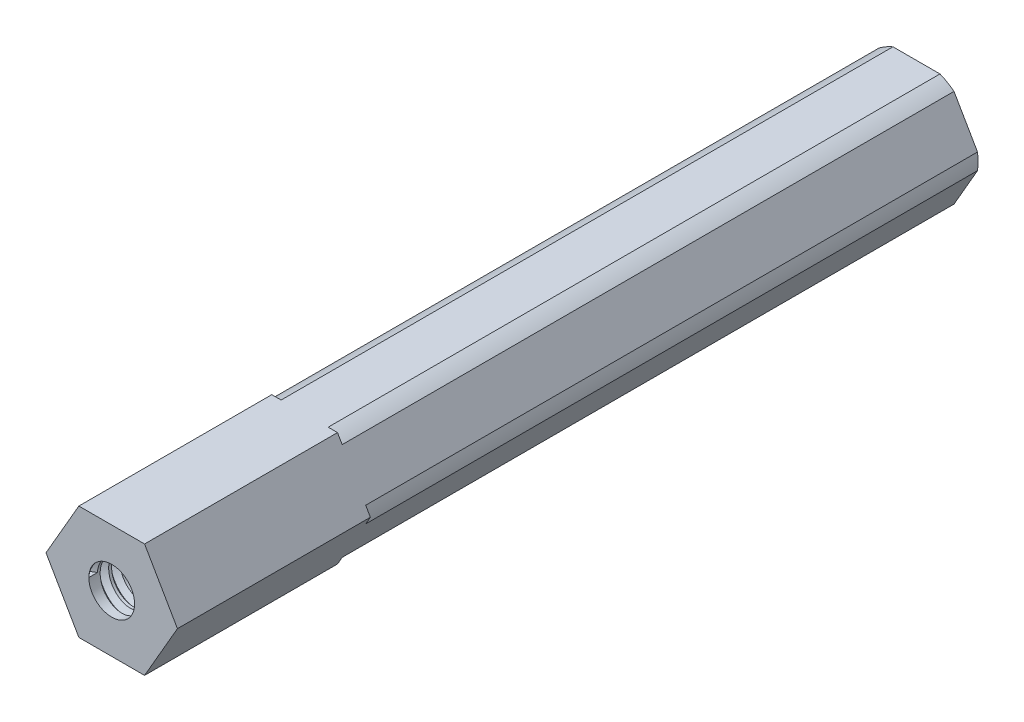
SolidWorks part; units mm, degrees
material "7075-T6 (SN)"
ref_plane "Alzado" through (0, 0, 0) normal (0, 0, 1) x (1, 0, 0)
ref_plane "Planta" through (0, 0, 0) normal (0, 1, 0) x (1, 0, 0)
ref_plane "Vista lateral" through (0, 0, 0) normal (1, 0, 0) x (0, 0, -1)
sketch "Croquis2" plane through (0, 0, 0) normal (0, 0, 1) x (1, 0, 0)
  line L1 (3.6662, -6.35) -> (7.3323, 0)
  line L2 (7.3323, 0) -> (3.6662, 6.35)
  line L3 (3.6662, 6.35) -> (-3.6662, 6.35)
  line L4 (-3.6662, 6.35) -> (-7.3323, 0)
  line L5 (-7.3323, 0) -> (-3.6662, -6.35)
  line L6 (-3.6662, -6.35) -> (3.6662, -6.35)
  circle A0 centre (0, 0) radius 6.35 construction
  dimension "D1" = 12.7
extrude "Extrusión Hex Profile" add sketch "Croquis2" along normal mid plane 89.789
sketch "Croquis3" plane through (0, 0, 0) normal (0, 0, 1) x (1, 0, 0)
  circle A0 centre (0, 0) radius 2.5527
  dimension "D1" = 5.1054
extrude "Tap Hole 1" cut sketch "Croquis3" against normal blind 19.05 from surface starting at face at (0, 0, 44.8945)
extrude "Tap Hole 2" cut sketch "Croquis3<3>" along normal blind 19.05 from surface starting at face at (0, 0, -44.8945)
sketch "Croquis3<3>" plane through (0, 0, 0) normal (0, 0, 1) x (1, 0, 0) same geometry as "Croquis3"
sketch "Croquis7" plane through (0, 0, 0) normal (0, 0, 1) x (1, 0, 0)
  circle A0 centre (0, 0) radius 6.8707
  dimension "D1" = 13.7414
extrude "ThunderHex" cut sketch "Croquis7" along normal offset from surface (68.2625 mm away) 21.5265 from surface flip side to cut up to face at (2.5527, 0, 44.8945) starting at face at (2.5527, 0, -44.8945)
sketch "Croquis8" plane through (0, 0, 0) normal (0, 1, 0) x (1, 0, 0)
  line L0 (0, -44.8945) -> (-5.5562, -44.8945) construction
  line L1 (3.6662, -44.8945) -> (-3.6662, -44.8945) construction
  line L3 (0, -44.8945) -> (0, 0) construction
  line L4 (-5.5562, -44.8945) -> (-6.35, -44.1008)
  line L5 (-6.35, -44.1008) -> (-6.35, -43.307)
  line L6 (-6.35, -43.307) -> (-5.9055, -43.307)
  line L7 (-5.9055, -43.307) -> (-5.9055, -41.7195)
  line L8 (-5.9055, -41.7195) -> (-12.7, -41.7195)
  line L9 (-12.7, -41.7195) -> (-12.7, -44.8945)
  line L10 (-12.7, -44.8945) -> (-5.5562, -44.8945)
  line L11 (-3.6662, -44.8945) -> (-7.3323, -44.8945) construction
  dimension "D1" = 11.811
  dimension "D2" = 12.7
  dimension "D3" = 45
  dimension "D4" = 0.7937
  dimension "D6" = 0.7937
  dimension "D7" = 3.175
  dimension "D8" = 25.4
revolve "Retaining Ring 1" [suppressed] cut sketch "Croquis8" angle 360 about L3
sketch "Croquis9" plane through (0, 0, 0) normal (0, -1, 0) x (1, 0, 0)
  line L0 (0, -44.8945) -> (-5.5562, -44.8945) construction
  line L3 (0, -44.8945) -> (0, 0) construction
  line L4 (-5.5562, -44.8945) -> (-6.35, -44.1008)
  line L5 (-6.35, -44.1008) -> (-6.35, -43.307)
  line L6 (-6.35, -43.307) -> (-5.9055, -43.307)
  line L7 (-5.9055, -43.307) -> (-5.9055, -41.7195)
  line L8 (-5.9055, -41.7195) -> (-12.7, -41.7195)
  line L9 (-12.7, -41.7195) -> (-12.7, -44.8945)
  line L10 (-12.7, -44.8945) -> (-5.5562, -44.8945)
  line L12 (-2.6237, -44.8945) -> (2.6237, -44.8945) construction
  line L13 (-6.8111, -44.8945) -> (-4.1874, -44.8945) construction
  dimension "D1" = 11.811
  dimension "D2" = 12.7
  dimension "D3" = 45
  dimension "D4" = 0.7937
  dimension "D6" = 0.7937
  dimension "D7" = 3.175
  dimension "D8" = 25.4
revolve "Retaining Ring 2" [suppressed] cut sketch "Croquis9" angle 360 about L3
sketch "Croquis10" plane through (0, 0, 0) normal (0, 1, 0) x (1, 0, 0)
  line L0 (0, -44.8945) -> (0, 0) construction
  line L1 (3.6662, -44.8945) -> (-3.6662, -44.8945) construction
  line L2 (0, -44.8945) -> (-5.5562, -44.8945) construction
  line L3 (-3.6662, -44.8945) -> (-7.3323, -44.8945) construction
  line L4 (-5.5562, -44.8945) -> (-6.35, -44.1008)
  line L5 (-6.35, -44.1008) -> (-6.35, -36.9443)
  line L6 (-6.35, -36.9443) -> (-9.525, -36.9443)
  line L7 (-9.525, -36.9443) -> (-9.525, -44.8945)
  line L8 (-9.525, -44.8945) -> (-5.5562, -44.8945)
  dimension "D2" = 12.7
  dimension "D1" = 45
  dimension "D3" = 0.7937
  dimension "D4" = 7.9502
  dimension "D5" = 19.05
revolve "Round End 1" [suppressed] cut sketch "Croquis10" angle 360 about L0
sketch "Croquis12" plane through (0, 0, 0) normal (0, -1, 0) x (1, 0, 0)
  line L0 (0, -44.8945) -> (0, 0) construction
  line L2 (0, -44.8945) -> (-5.5562, -44.8945) construction
  line L4 (-5.5562, -44.8945) -> (-6.35, -44.1008)
  line L5 (-6.35, -44.1008) -> (-6.35, -36.9443)
  line L6 (-6.35, -36.9443) -> (-9.525, -36.9443)
  line L7 (-9.525, -36.9443) -> (-9.525, -44.8945)
  line L8 (-9.525, -44.8945) -> (-5.5562, -44.8945)
  line L9 (-2.6237, -44.8945) -> (2.6237, -44.8945) construction
  dimension "D1" = 45
  dimension "D3" = 0.7937
  dimension "D4" = 7.9502
  dimension "D2" = 12.7
  dimension "D5" = 19.05
revolve "Round End 2" [suppressed] cut sketch "Croquis12" angle 360 about L0
thread "Rosca1" pitch 1.27 method cut profile "Perfil de rosca1" start angle 0, offset 0, length 0, pitch 1.27, diameter 5.1054
ref_plane "Plano1" through (-2.5527, 0, 44.8945) normal (0, -1, 0) x (-1, 0, 0)
sketch "Perfil de rosca1" plane through (-2.5527, 0, 44.8945) normal (0, -1, 0) x (-1, 0, 0)
  line L0 (0, 0) -> (0, 1.27) construction
  line L1 (0, 0) -> (0.6874, 0.3969)
  line L2 (0.6874, 0.3969) -> (0.6874, 0.5556)
  line L3 (0.6874, 0.5556) -> (0, 0.9525)
  line L4 (0.6874, 0.4762) -> (0, 0.4762) construction
  line L11 (0, 0) -> (0, 0.9525)
  point P2 (0, 0)
  dimension "Pitch" = 1.27
  dimension "Profile_Angle" = 60
  dimension "Profile_Land" = 0.1588
  dimension "Profile_Height" = 0.6874
thread "Rosca2" pitch 1.27 method cut profile "Perfil de rosca2" start angle 0, offset 0, length 0, pitch 1.27, diameter 5.1054
ref_plane "Plano2" through (2.5527, 0, -44.8945) normal (0, -1, 0) x (1, 0, 0)
sketch "Perfil de rosca2" plane through (2.5527, 0, -44.8945) normal (0, -1, 0) x (1, 0, 0)
  line L0 (0, 0) -> (0, 1.27) construction
  line L1 (0, 0) -> (0.6874, 0.3969)
  line L2 (0.6874, 0.3969) -> (0.6874, 0.5556)
  line L3 (0.6874, 0.5556) -> (0, 0.9525)
  line L4 (0.6874, 0.4762) -> (0, 0.4762) construction
  line L11 (0, 0) -> (0, 0.9525)
  point P2 (0, 0)
  dimension "Pitch" = 1.27
  dimension "Profile_Angle" = 60
  dimension "Profile_Land" = 0.1588
  dimension "Profile_Height" = 0.6874
equation "\"HexOD\"= 0.5pulgadas"
equation "\"Largo\"= 3.535pulgadas"
equation "\"D1@Croquis2\"=\"HexOD\""
equation "\"D1@Extrusión Hex Profile\" = \"Largo\""
equation "\"TapHole\"= IIF ( \"HexOD\" = 0.5pulgadas , 0.2010pulgadas , 0.190pulgadas )"
equation "\"D1@Croquis3\"=\"TapHole\""
equation "\"ProTapHole\"= 0.75pulgadas"
equation "\"D1@Tap Hole 1\" = \"ProTapHole\""
equation "\"D1@Tap Hole 2\" = \"ProTapHole\""
equation "\"ThunderHex\"= IIF ( \"HexOD\" = 0.5pulgadas , 0.541pulgadas , 0.4035pulgadas )"
equation "\"D1@Croquis7\"=\"ThunderHex\""
equation "\"D2@Croquis8\"=\"HexOD\""
equation "\"D1@Croquis8\"=if(\"HexOD\"=0.5pulgadas, 0.465pulgadas, 0.35pulgadas )"
equation "\"D2@Croquis9\"=\"HexOD\""
equation "\"D1@Croquis9\"=if(\"HexOD\"=0.5pulgadas, 0.465pulgadas, 0.35pulgadas )"
equation "\"D8@Croquis8\"=\"HexOD\"*2"
equation "\"D8@Croquis9\"=\"HexOD\"*2"
equation "\"D5@Croquis10\"=\"HexOD\"*1.5"
equation "\"D5@Croquis12\"=\"HexOD\"*1.5"
equation "\"D4@Croquis10\"=if( \"D2@Croquis10\"=<0.375, 0.28, 0.313)"
equation "\"D4@Croquis12\"=if( \"D2@Croquis10\"=<0.375, 0.28, 0.313)"
